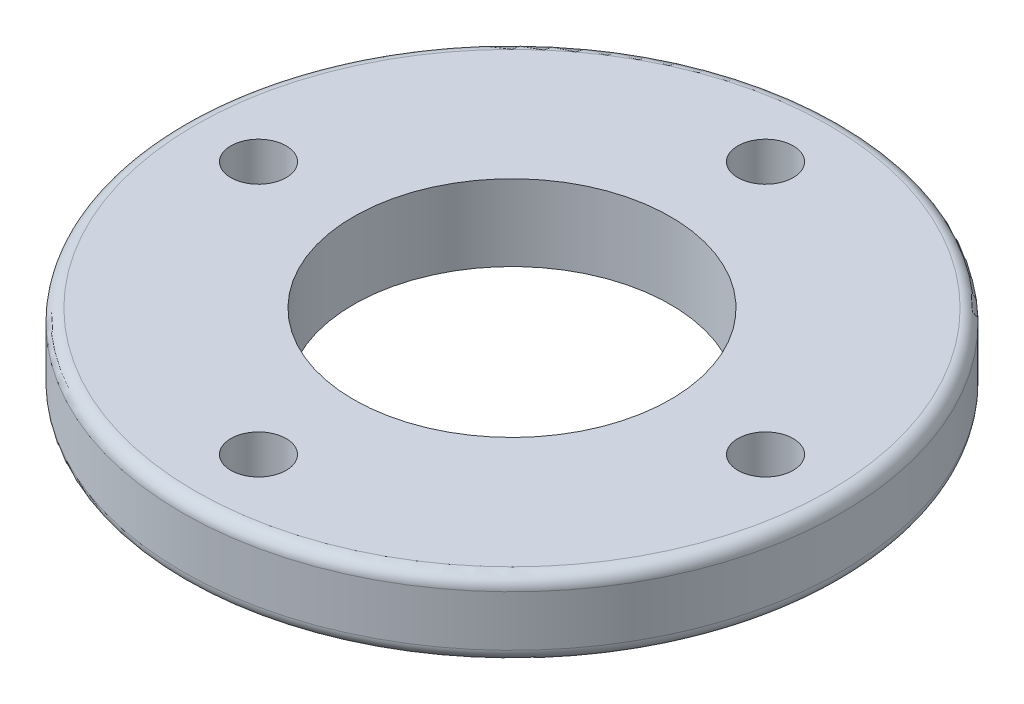
SolidWorks part; units mm, degrees
ref_plane "Front" through (0, 0, 0) normal (0, 0, 1) x (1, 0, 0)
ref_plane "Top" through (0, 0, 0) normal (0, 1, 0) x (1, 0, 0)
ref_plane "Right" through (0, 0, 0) normal (1, 0, 0) x (0, 0, -1)
sketch "Sketch1" plane through (0, 0, 0) normal (0, 1, 0) x (1, 0, 0)
  circle A0 centre (0, 0) radius 13
  dimension "D1" = 26
extrude "Boss-Extrude1" add sketch "Sketch1" along normal blind 3
sketch "Sketch2" plane through (0, 3, 0) normal (0, 1, 0) x (1, 0, 0)
  line L0 (0, 0) -> (0, 13) construction
  circle A0 centre (0, 0) radius 13 construction
  circle A1 centre (0, 10) radius 1.09
  dimension "D1" = 2.18
  dimension "D2" = 10
extrude "Cut-Extrude1" cut sketch "Sketch2" against normal up to surface (3 mm away) up to face at (0, 0, 13)
sketch "Sketch3" plane through (0, 3, 0) normal (0, 1, 0) x (1, 0, 0)
  point P0 (0, 0)
sketch "Sketch4" plane through (0, 0, 0) normal (0, 0, 1) x (1, 0, 0)
  line L0 (0, 0) -> (0, 3) construction
pattern_circular "CirPattern1" count 4 over 360 about axis through (0, 0, 0) along (0, 1, 0) of "Cut-Extrude1"
fillet "Fillet1" radius 0.5 2 edges at (0, 0, 13) (0, 3, 13)
sketch "Sketch5" plane through (0, 3, 0) normal (0, 1, 0) x (1, 0, 0)
  circle A0 centre (0, 0) radius 6.25
  dimension "D1" = 12.5
extrude "Cut-Extrude2" cut sketch "Sketch5" against normal mid plane 50
